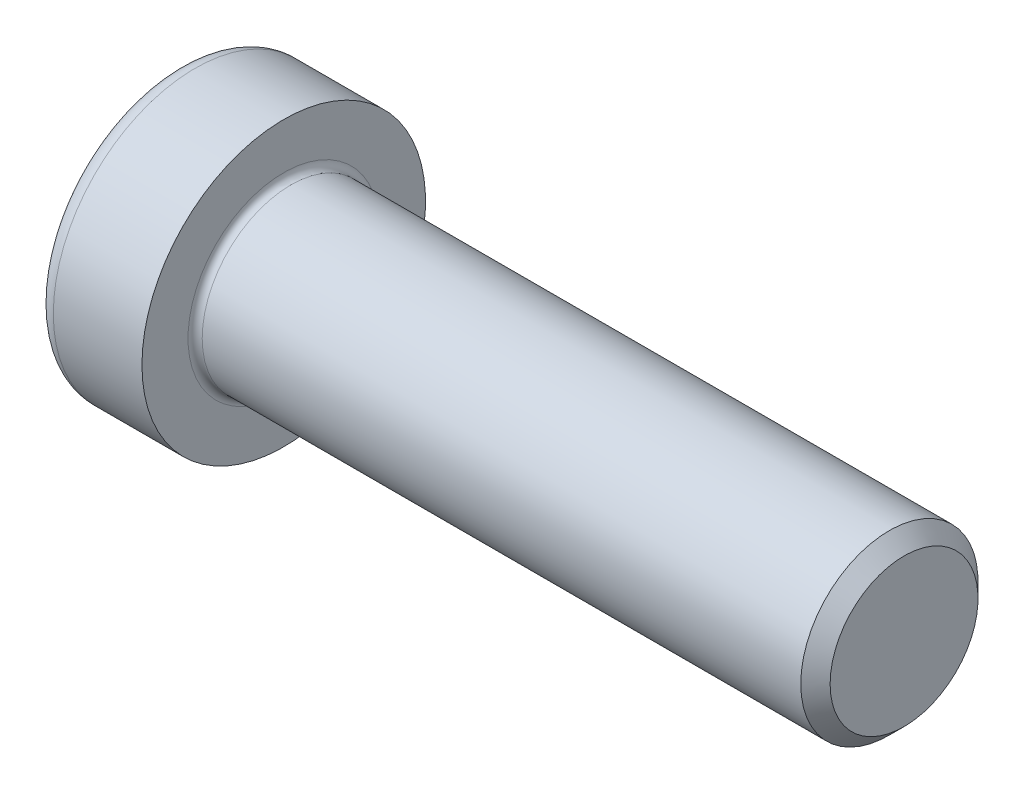
SolidWorks part; units mm, degrees
revolve "Base-Revolve" add sketch "BodySke"
sketch "BodySke" plane through (0, 0, 0) normal (0, 0, 1) x (1, 0, 0)
  line L0 (0, 0) -> (0, 8)
  line L1 (0, 8) -> (6, 8)
  line L2 (6, 8) -> (6, 5)
  line L3 (6, 5) -> (40.172, 5)
  line L4 (41, 4.172) -> (41, 0)
  line L5 (41, 0) -> (0, 0)
  line L6 (-31.75, 0) -> (127, 0) construction
  line L8 (41, 4.172) -> (40.172, 5)
  line L10 (41, -4.172) -> (40.172, -5) construction
  line L11 (7.5, 4.525) -> (7.5, -1.825) construction
  line L12 (6, 4.525) -> (6, -1.825) construction
  line L13 (-19, 4.525) -> (-19, -1.825) construction
  dimension "Diameter" = 10
  dimension "Head_dia" = 16
cosmetic thread "ThreadCosmetic" [suppressed]
fillet "Fillet1" radius 0.4 1 edges at (6, 0, 5)
fillet "Fillet2" radius 1 1 edges at (0, 0, 8)
ref_plane "Plane1" through (0, 0, 0) normal (0, 0, 1) x (1, 0, 0)
ref_plane "Plane2" through (0, 0, 0) normal (0, 1, 0) x (1, 0, 0)
ref_plane "Plane3" through (0, 0, 0) normal (1, 0, 0) x (0, 0, -1)
sketch "Sketch2" plane through (0, 0, 0) normal (0, 0, 1) x (1, 0, 0)
  line L0 (0, 3.5) -> (4.5, 3.5)
  line L1 (4.5, 3.5) -> (6.5207, 0)
  line L2 (-31.75, 0) -> (127, 0) construction
  line L3 (6.5207, 0) -> (0, 0)
  line L4 (0, 0) -> (0, 3.5)
  line L6 (0, 0) -> (47.625, 0) construction
  dimension "D1" = 3.5
  dimension "D2" = 60
revolve "Hex-PreBroach" cut sketch "Sketch2" angle 360 about L6
sketch "Sketch3" plane through (0, 0, 0) normal (-1, 0, 0) x (0, 0.5, 0.866)
  line L0 (2.0207, 3.5) -> (-2.0207, 3.5)
  line L1 (-2.0207, 3.5) -> (-4.0415, 0)
  line L2 (2.0207, 3.5) -> (4.0415, 0)
  line L3 (2.0207, -3.5) -> (4.0415, 0)
  line L4 (2.0207, -3.5) -> (-2.0207, -3.5)
  line L5 (-2.0207, -3.5) -> (-4.0415, 0)
  dimension "D1" = 3.5
  dimension "D2" = 3.5
extrude "Hex" cut sketch "Sketch3" against normal blind 4.5
sketch "ThdSchSke" plane through (0, 0, 0) normal (0, 0, 1) x (1, 0, 0)
  line L0 (10.5, -4.172) -> (9.9202, -5)
  line L1 (10.5, -4.172) -> (11.0798, -5)
  line L2 (11.0798, -5) -> (11.0798, -6.25)
  line L3 (-3.175, 0) -> (5.1513, 0) construction
  line L4 (0, 7) -> (0, -7) construction
  line L5 (11.0798, -6.25) -> (9.9202, -6.25)
  line L6 (9.9202, -6.25) -> (9.9202, -5)
  dimension "Diameter" = 10
  dimension "Thread_minor" = 8.344
  dimension "Start" = 10.5
revolve "ThreadSchematic" [suppressed] cut sketch "ThdSchSke" angle 360 about L3
pattern_linear "ThdSchPat" [suppressed]
equation "\"D2@Sketch3\" = \"Hex_size@Sketch3\" / 2"
equation "\"D1@Sketch3\" = \"Hex_size@Sketch3\" / 2"
equation "\"D1@Sketch2\" = \"Hex_size@Sketch3\" / 2"
equation "\"Thread_minor@ThreadCosmetic\"  =  \"Minor_dia@BodySke\""
equation "\"Depth@Sketch2\" =  \"Key_eng@Hex\""
equation "\"Thread_length@ThreadCosmetic\" = ((sgn( (\"Length@BodySke\" - \"Advance@BodySke\" * 3.0) - \"Thread_nom@BodySke\" )-1)*( (\"Length@BodySke\" - \"Advance@BodySke\" * 3.0) - \"Thread_nom@BodySke\" ))/-2+ \"Thread_nom@BodySke\""
equation "\"Thread_minor@ThdSchSke\" = \"Minor_dia@BodySke\""
equation "\"Diameter@ThdSchSke\" = \"Diameter@BodySke\""
equation "\"Overcut@ThdSchSke\" = \"Diameter@BodySke\" * 1.25"
equation "\"Start@ThdSchSke\" = \"Head_ht@BodySke\" + \"Length@BodySke\" - \"Thread_length@ThreadCosmetic\"  '---Non-countersunk---"
equation "\"Num_threads@ThdSchPat\" = int( \"Thread_length@ThreadCosmetic\" / \"Advance@BodySke\" + 0.999 )  + 1"
equation "\"Advance@ThdSchPat\" = \"Thread_length@ThreadCosmetic\" /  (\"Num_threads@ThdSchPat\" - 1) 'relax it"
equation "\"Num_threads@ThdSchPat\" = \"Num_threads@ThdSchPat\" - sgn( \"Num_threads@ThdSchPat\" - 1) '---chamfered tips only---"
